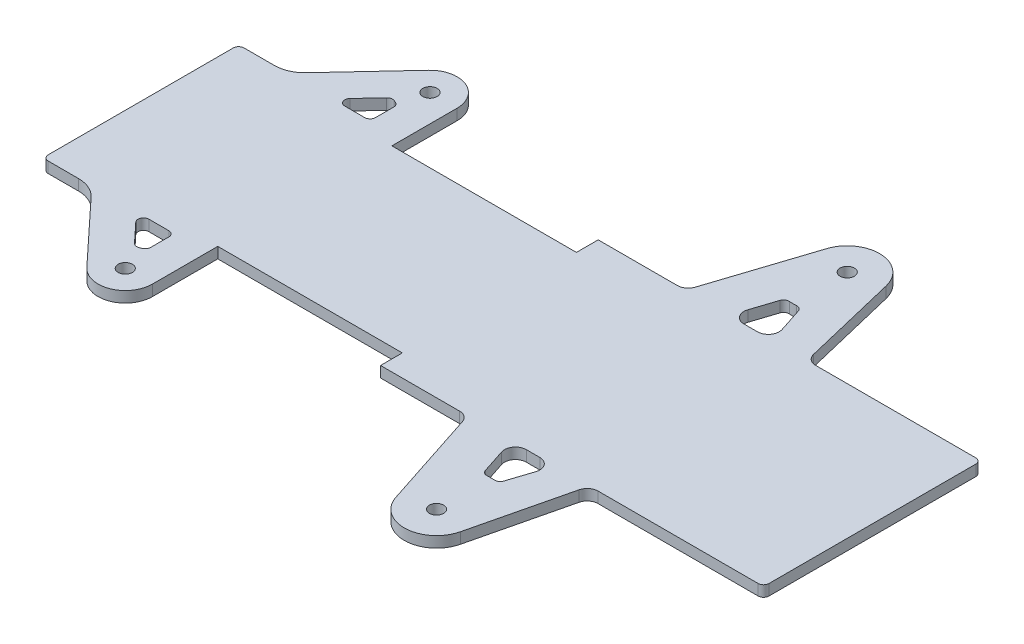
SolidWorks part; units mm, degrees
ref_plane "Front Plane" through (0, 0, 0) normal (0, 0, 1) x (1, 0, 0)
ref_plane "Top Plane" through (0, 0, 0) normal (0, 1, 0) x (1, 0, 0)
ref_plane "Right Plane" through (0, 0, 0) normal (1, 0, 0) x (0, 0, -1)
sketch "Sketch1" plane through (0, 0, 0) normal (0, 1, 0) x (1, 0, 0)
  line L0 (-64.5699, 0) -> (82.804, 0) construction
  line L1 (26.924, -25.4) -> (-26.924, -25.4)
  line L2 (71.424, -59.917) -> (71.424, 59.917) construction
  line L3 (26.924, 25.4) -> (-26.924, 25.4)
  line L4 (26.924, 25.4) -> (26.924, 31.75)
  line L5 (26.924, -25.4) -> (-26.924, 25.4) construction
  line L6 (26.924, 25.4) -> (-26.924, -25.4) construction
  line L7 (-26.924, 25.4) -> (-26.924, 28.575)
  line L8 (-47.4926, -28.575) -> (-39.004, -37.6792)
  line L9 (-26.924, 28.575) -> (-26.924, 44.45)
  line L10 (-60.5155, -28.575) -> (-40.667, -49.8629)
  line L11 (-26.924, -44.45) -> (-26.924, -25.4)
  line L12 (-46.228, -28.575) -> (-26.924, 28.575) construction
  line L13 (-46.228, 28.575) -> (-26.924, -28.575) construction
  line L14 (52.324, -31.75) -> (26.924, -31.75)
  line L15 (138.684, -31.75) -> (138.684, 31.75)
  line L16 (138.684, 31.75) -> (87.884, 31.75)
  line L17 (26.924, -31.75) -> (26.924, -25.4)
  line L18 (138.684, -31.75) -> (26.924, 31.75) construction
  line L19 (138.684, 31.75) -> (26.924, -31.75) construction
  line L20 (52.324, 31.75) -> (62.6076, 63.2401)
  line L21 (52.324, -31.75) -> (62.6076, -63.2401)
  line L22 (52.324, 31.75) -> (26.924, 31.75)
  line L23 (87.884, 31.75) -> (80.5851, 62.1188)
  line L24 (138.684, -31.75) -> (87.884, -31.75)
  line L25 (87.884, -31.75) -> (80.5851, -62.1188)
  line L26 (77.774, 31.75) -> (65.074, 31.75)
  line L27 (65.074, 31.75) -> (69.142, 44.2069)
  line L28 (77.774, 31.75) -> (73.706, 44.2069)
  line L29 (77.774, -31.75) -> (73.706, -44.2069)
  line L30 (65.074, -31.75) -> (69.142, -44.2069)
  line L31 (77.774, -31.75) -> (65.074, -31.75)
  line L32 (-34.8615, -44.45) -> (-34.8615, 44.45) construction
  line L33 (-60.5155, 28.575) -> (-40.667, 49.8629)
  line L34 (-74.803, -28.575) -> (-60.5155, -28.575)
  line L35 (-74.803, -28.575) -> (-74.803, 28.575)
  line L36 (-74.803, 28.575) -> (-60.5155, 28.575)
  line L38 (-74.803, -28.575) -> (-46.228, 28.575) construction
  line L39 (-74.803, 28.575) -> (-46.228, -28.575) construction
  line L40 (-36.449, -28.575) -> (-36.449, -36.6729)
  line L41 (-47.4926, -28.575) -> (-36.449, -28.575)
  line L42 (-47.4926, 28.575) -> (-36.449, 28.575)
  line L43 (-36.449, 28.575) -> (-36.449, 36.6729)
  line L44 (-47.4926, 28.575) -> (-39.004, 37.6792)
  circle A0 centre (71.424, 59.917) radius 2.0828
  arc A1 (80.5851, 62.1188) -> (62.6076, 63.2401) centre (71.424, 59.917) ccw
  arc A2 (80.5851, -62.1188) -> (62.6076, -63.2401) centre (71.424, -59.917) cw
  arc A3 (69.142, -44.2069) -> (73.706, -44.2069) centre (71.424, -59.917) cw
  arc A4 (69.142, 44.2069) -> (73.706, 44.2069) centre (71.424, 59.917) ccw
  circle A5 centre (-34.8615, 44.45) radius 2.0828
  circle A6 centre (71.424, -59.917) radius 2.0828
  arc A7 (-26.924, 44.45) -> (-40.667, 49.8629) centre (-34.8615, 44.45) ccw
  arc A8 (-40.667, -49.8629) -> (-26.924, -44.45) centre (-34.8615, -44.45) ccw
  circle A9 centre (-34.8615, -44.45) radius 2.0828
  arc A10 (-36.449, 36.6729) -> (-39.004, 37.6792) centre (-34.8615, 44.45) cw
  arc A11 (-36.449, -36.6729) -> (-39.004, -37.6792) centre (-34.8615, -44.45) ccw
  point P0 (0, 0)
  point P8 (-36.576, 0)
  point P20 (71.424, 0)
  point P31 (138.684, 0)
  point P37 (71.424, 31.75)
  point P42 (71.424, -31.75)
  point P43 (-60.5155, 0)
  point P46 (-34.8615, 0)
  dimension "D9" = 4.1656
  dimension "D10" = 50.8
  dimension "D13" = 7.9375
  dimension "D15" = 15.875
  dimension "D16" = 28.575
  dimension "D18" = 4.1656
  dimension "D19" = 15.875
  dimension "D1" = 53.848
  dimension "D2" = 50.8
  dimension "D3" = 57.15
  dimension "D4" = 19.304
  dimension "D5" = 111.76
  dimension "D6" = 63.5
  dimension "D7" = 119.834
  dimension "D8" = 44.5
  dimension "D11" = 25.4
  dimension "D12" = 63.5
  dimension "D14" = 12.7
  dimension "D17" = 88.9
  dimension "D21" = 9.525
extrude "Boss-Extrude1" add sketch "Sketch1" along normal blind 3.175
fillet "Fillet1" radius 1.5875 4 edges at (73.706, 1.5875, -44.2069) (69.142, 1.5875, -44.2069) (73.706, 1.5875, 44.2069) (69.142, 1.5875, 44.2069)
fillet "Fillet2" radius 3.175 4 edges at (77.774, 1.5875, 31.75) (65.074, 1.5875, 31.75) (77.774, 1.5875, -31.75) (65.074, 1.5875, -31.75)
fillet "Fillet3" radius 1.5875 2 edges at (138.684, 1.5875, -31.75) (138.684, 1.5875, 31.75)
fillet "Fillet4" radius 3.175 4 edges at (52.324, 1.5875, -31.75) (87.884, 1.5875, -31.75) (87.884, 1.5875, 31.75) (52.324, 1.5875, 31.75)
fillet "Fillet5" radius 8.89 2 edges at (-60.5155, 1.5875, -28.575) (-60.5155, 1.5875, 28.575)
fillet "Fillet6" radius 1.5875 2 edges at (-74.803, 1.5875, 28.575) (-74.803, 1.5875, -28.575)
fillet "Fillet7" radius 1.5875 2 edges at (-36.449, 1.5875, -28.575) (-36.449, 1.5875, 28.575)
fillet "Fillet8" radius 1.5875 6 edges at (-36.449, 1.5875, 36.6729) (-39.004, 1.5875, 37.6792) (-47.4926, 1.5875, 28.575) (-36.449, 1.5875, -36.6729) (-39.004, 1.5875, -37.6792) (-47.4926, 1.5875, -28.575)
